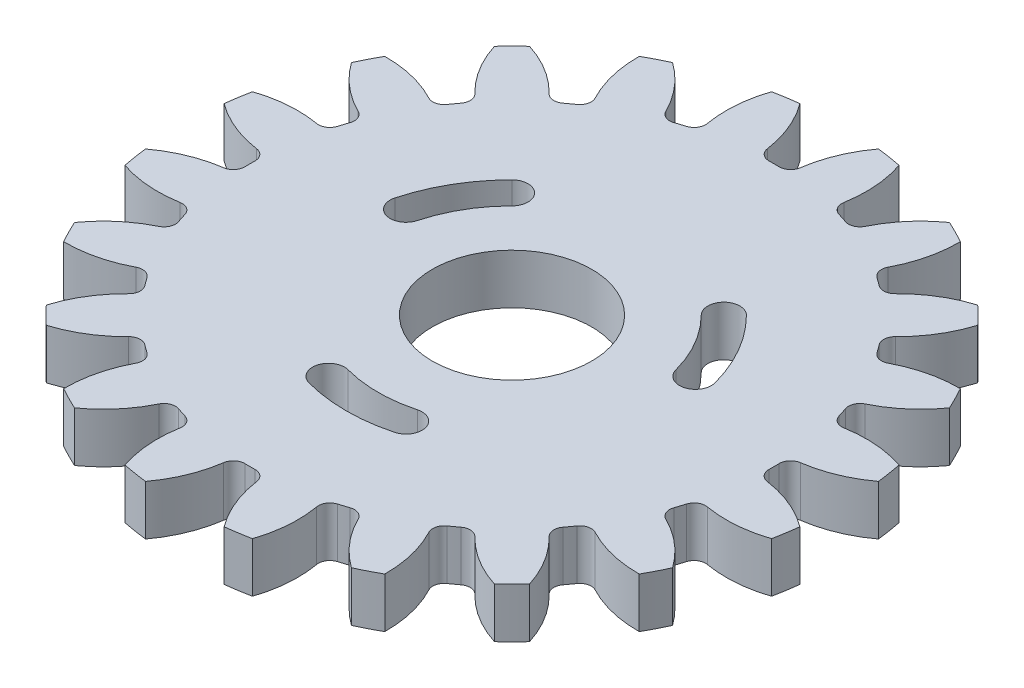
SolidWorks part; units mm, degrees
material "Acrylic (Medium-high impact)"
ref_plane "Front Plane" through (0, 0, 0) normal (0, 0, 1) x (1, 0, 0)
ref_plane "Top Plane" through (0, 0, 0) normal (0, 1, 0) x (1, 0, 0)
ref_plane "Right Plane" through (0, 0, 0) normal (1, 0, 0) x (0, 0, -1)
sketch "Sketch2" plane through (0, 0, 0) normal (0, 1, 0) x (1, 0, 0)
  circle A0 centre (0, 0) radius 33
  circle A1 centre (0, 0) radius 7.975
  dimension "D1" = 15.95
  dimension "D2" = 66
extrude "Boss-Extrude1" add sketch "Sketch2" along normal blind 5
sketch "Sketch3" plane through (0, 5, 0) normal (0, 1, 0) x (1, 0, 0)
  line L0 (0, 0) -> (0, 33) construction
  line L1 (-1.5456, 26.2045) -> (0, 0) construction
  line L2 (0, 23.449) -> (4.1879, 11.9429) construction
  arc A0 (1.5456, 26.2045) -> (-1.5456, 26.2045) centre (0, 0) ccw
  arc A1 (2.3538, 29.9075) -> (-2.3538, 29.9075) centre (0, 0) ccw construction
  arc A2 (3.9334, 32.7647) -> (-3.9334, 32.7647) centre (0, 0) ccw
  circle A3 centre (0, 0) radius 33 construction
  arc A5 (-3.9334, 32.7647) -> (-1.5456, 26.2045) centre (-13.7254, 25.4861) cw
  arc A6 (3.9334, 32.7647) -> (1.5456, 26.2045) centre (13.7254, 25.4861) ccw
  point P3 (3.744, 11.8925)
  point P16 (-2.2603, 29.659)
  dimension "D1" = 60
  dimension "D2" = 6.75
  dimension "D3" = 20
  dimension "D4" = 4.7124
extrude "Cut-Extrude1" cut sketch "Sketch3" against normal through all
fillet "Fillet1" radius 1.14 2 edges at (1.5456, 2.5, -26.2045) (-1.5456, 2.5, -26.2045)
pattern_circular "CirPattern1" count 20 over 360 about axis through (0, 5, 0) along (0, -1, 0) of "Cut-Extrude1", "Fillet1" reverse direction yes
sketch "Sketch4" plane through (0, 0, 0) normal (0, -1, 0) x (1, 0, 0)
  line L0 (0, 0) -> (0, 15) construction
  line L1 (-3.8823, 14.4889) -> (0, 0) construction
  line L2 (0, 0) -> (3.8823, 14.4889) construction
  circle A0 centre (0, 0) radius 15 construction
  arc A5 (-3.8823, 14.4889) -> (3.8823, 14.4889) centre (0, 0) cw construction
  arc A6 (4.2964, 16.0344) -> (-4.2964, 16.0344) centre (0, 0) ccw
  arc A7 (3.4682, 12.9434) -> (-3.4682, 12.9434) centre (0, 0) ccw
  arc A8 (3.4682, 12.9434) -> (4.2964, 16.0344) centre (3.8823, 14.4889) ccw
  arc A9 (-4.2964, 16.0344) -> (-3.4682, 12.9434) centre (-3.8823, 14.4889) ccw
  arc A10 (14.4889, -3.8823) -> (10.6066, -10.6066) centre (0, 0) cw construction
  arc A11 (11.738, -11.738) -> (16.0344, -4.2964) centre (0, 0) ccw
  arc A12 (9.4752, -9.4752) -> (12.9434, -3.4682) centre (0, 0) ccw
  arc A13 (9.4752, -9.4752) -> (11.738, -11.738) centre (10.6066, -10.6066) ccw
  arc A14 (16.0344, -4.2964) -> (12.9434, -3.4682) centre (14.4889, -3.8823) ccw
  arc A15 (-10.6066, -10.6066) -> (-14.4889, -3.8823) centre (0, 0) cw construction
  arc A16 (-16.0344, -4.2964) -> (-11.738, -11.738) centre (0, 0) ccw
  arc A17 (-12.9434, -3.4682) -> (-9.4752, -9.4752) centre (0, 0) ccw
  arc A18 (-12.9434, -3.4682) -> (-16.0344, -4.2964) centre (-14.4889, -3.8823) ccw
  arc A19 (-11.738, -11.738) -> (-9.4752, -9.4752) centre (-10.6066, -10.6066) ccw
  point P5 (0, 15)
  point P10 (0, 0)
  point P16 (0, 0)
  point P19 (12.9904, -7.5)
  point P26 (-12.9904, -7.5)
  point P31 (0, 0)
  point P32 (0, 0)
  point P33 (0, 0)
  point P36 (0, 0)
  dimension "D1" = 30
  dimension "D3" = 30
  dimension "D2" = 1.6
  dimension "D4" = 3
extrude "Cut-Extrude2" cut sketch "Sketch4" against normal through all
equation "\"No. of teeth\" = 20"
equation "\"Module\"= 3"
equation "\"Bore diameter\" = 15.95"
equation "\"Pressure angle\"= 20"
equation "\"Outer diameter\"= ( \"No. of teeth\" + 2 ) * \"Module\""
equation "\"Pitch diameter\"= \"No. of teeth\" * \"Module\""
equation "\"Backlash\" = 0"
equation "\"Arc length\"= ( ( \"Module\" * pi ) / 2 ) + \"Backlash\""
equation "\"Fillet radius\"= 0.38 * \"Module\""
equation "\"Tooth depth\"= IIF ( \"Module\" <= 1.25 , \"Module\" * 2.4 , \"Module\" * 2.25 )"
equation "\"D1@Sketch2\"=\"Bore diameter\""
equation "\"D2@Sketch2\"=\"Outer diameter\""
equation "\"D1@Sketch3\"=\"Pitch diameter\""
equation "\"D2@Sketch3\"=\"Tooth depth\""
equation "\"D3@Sketch3\"=\"Pressure angle\""
equation "\"D4@Sketch3\"=\"Arc length\""
equation "\"D1@Fillet1\"=\"Fillet radius\""
equation "\"D1@CirPattern1\"=\"No. of teeth\""
equation "\"Gear thickness\"= 5"
equation "\"D1@Boss-Extrude1\"=\"Gear thickness\""
